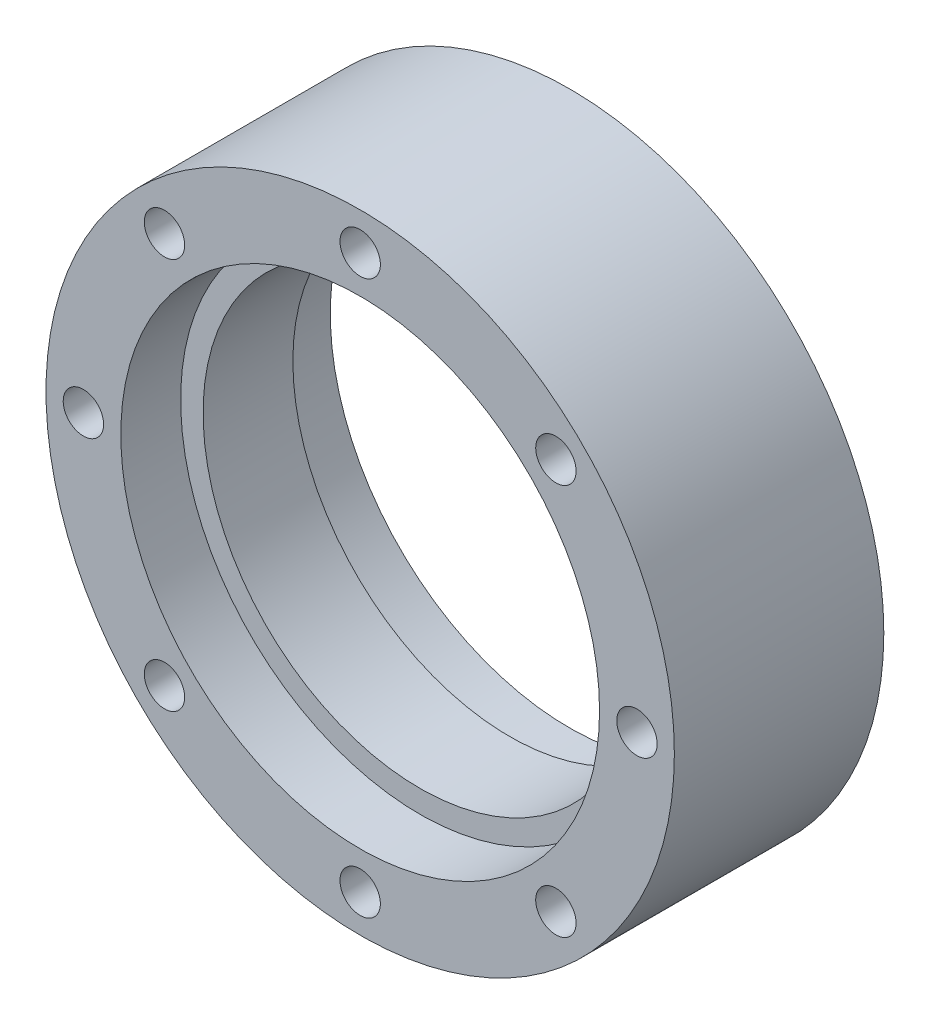
SolidWorks part; units mm, degrees
ref_plane "Front Plane" through (0, 0, 0) normal (0, 0, 1) x (1, 0, 0)
ref_plane "Top Plane" through (0, 0, 0) normal (0, 1, 0) x (1, 0, 0)
ref_plane "Right Plane" through (0, 0, 0) normal (1, 0, 0) x (0, 0, -1)
ref_axis "Z" through (0, 0, 8.25) along (0, 0, -1)
sketch "Sketch1" plane through (0, 0, 0) normal (0, 0, 1) x (1, 0, 0)
  circle A0 centre (0, 0) radius 21
  circle A1 centre (0, 0) radius 14.5
  dimension "D1" = 29
  dimension "D2" = 42
extrude "MainBody" add sketch "Sketch1" along normal blind 7 and the other way blind 7
sketch "Sketch2" plane through (0, 0, 7) normal (0, 0, 1) x (1, 0, 0)
  circle A0 centre (0, 0) radius 16
  dimension "D1" = 32
extrude "Cut-Extrude1" cut sketch "Sketch2" against normal blind 4
mirror "Mirror1" about plane through (0, 0, 0) normal (0, 0, 1) of "Cut-Extrude1"
sketch "Sketch3" plane through (0, 0, 0) normal (0, 0, 1) x (1, 0, 0)
  line L1 (0, 21) -> (0, 16) construction
  circle A0 centre (0, 18.5) radius 1.35
  circle A2 centre (0, 0) radius 21 construction
  circle A3 centre (0, 0) radius 16 construction
  circle A4 centre (0, 0) radius 18.5 construction
  dimension "D1" = 2.7
  dimension "D2" = 32
  dimension "D3" = 37
extrude "Cut-Extrude2" cut sketch "Sketch3" against normal through all both and the other way through all
sketch "Sketch4" plane through (0, 0, -7) normal (0, 0, -1) x (-1, 0, 0)
  circle A0 centre (0, 18.5) radius 2.25
  circle A1 centre (0, 18.5) radius 1.35 construction
  dimension "D1" = 4.5
extrude "Cut-Extrude4" cut sketch "Sketch4" against normal blind 2.5 and the other way through all
chamfer "Chamfer1" distance 0.1 angle 45 1 edges at (-1.35, 18.5, -4.5)
pattern_circular "CirPattern1" count 4 over 360 about axis through (0, 0, 8.25) along (0, 0, -1) of "Cut-Extrude2", "Cut-Extrude4", "Chamfer1"
pattern_circular "CirPattern2" count 8 over 360 about axis through (0, 0, 8.25) along (0, 0, -1) of "Cut-Extrude2"
equation "\"BearingBaseDistance\"= 6"
equation "\"BearingOD\"= 32"
equation "\"BearingHeight\"= 4"
equation "\"D1@Cut-Extrude1\"=\"BearingHeight\""
equation "\"D1@MainBody\" = \"BearingBaseDistance\" / 2 + \"BearingHeight\""
equation "\"D2@MainBody\" = \"BearingBaseDistance\" / 2 + \"BearingHeight\""
equation "\"D1@Sketch1\"=\"BearingOD\"-3"
equation "\"D1@Sketch2\"=\"BearingOD\""
equation "\"SeatsOD\"= \"BearingOD\" + 10"
equation "\"D2@Sketch1\"=\"SeatsOD\""
equation "\"D2@Sketch3\"=\"BearingOD\""
